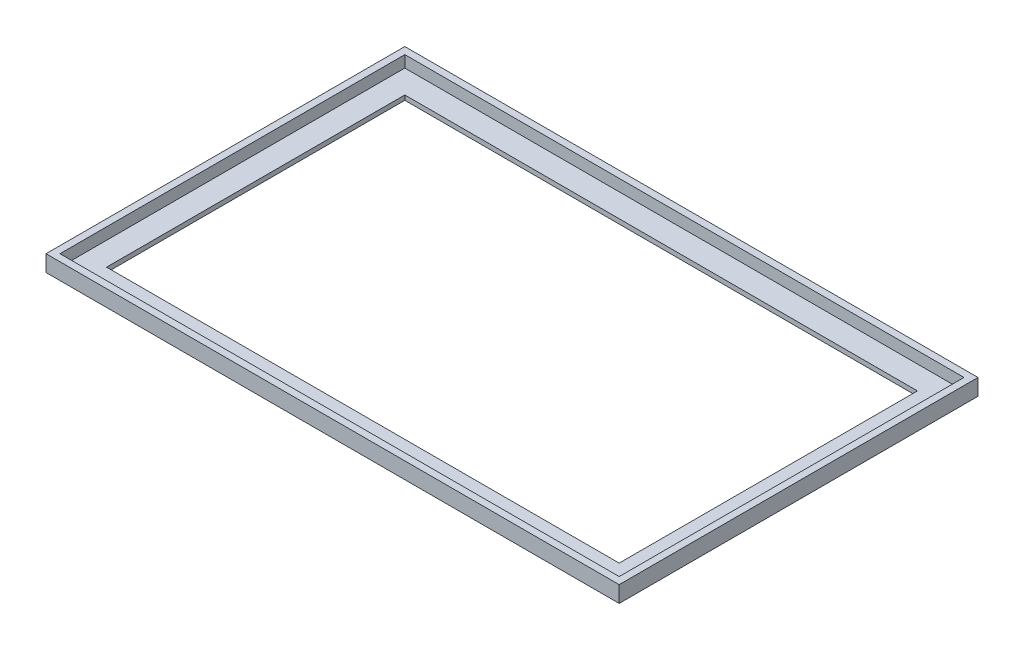
SolidWorks part; units mm, degrees
material "Alumina"
ref_plane "Front Plane" through (0, 0, 0) normal (0, 0, 1) x (1, 0, 0)
ref_plane "Top Plane" through (0, 0, 0) normal (0, 1, 0) x (1, 0, 0)
ref_plane "Right Plane" through (0, 0, 0) normal (1, 0, 0) x (0, 0, -1)
sketch "Sketch1" plane through (0, 0, 0) normal (0, 1, 0) x (1, 0, 0)
  line L1 (-123, -77) -> (123, -77)
  line L2 (-123, -77) -> (-123, 77)
  line L3 (-123, 77) -> (123, 77)
  line L4 (123, -77) -> (123, 77)
  line L5 (-123, -77) -> (123, 77) construction
  line L6 (-123, 77) -> (123, -77) construction
  point P0 (0, 0)
  dimension "D1" = 246
  dimension "D2" = 154
extrude "Boss-Extrude1" add sketch "Sketch1" against normal blind 7
sketch "Sketch2" plane through (0, 0, 0) normal (0, 1, 0) x (1, 0, 0)
  line L1 (-120, -74) -> (120, -74)
  line L2 (-120, -74) -> (-120, 74)
  line L3 (-120, 74) -> (120, 74)
  line L4 (120, -74) -> (120, 74)
  line L5 (-120, -74) -> (120, 74) construction
  line L6 (-120, 74) -> (120, -74) construction
  point P0 (0, 0)
  dimension "D1" = 240
  dimension "D2" = 148
extrude "Cut-Extrude1" cut sketch "Sketch2" against normal blind 5
sketch "Sketch3" plane through (0, -5, 0) normal (0, 1, 0) x (1, 0, 0)
  line L0 (120, 74) -> (-120, 74) construction
  line L1 (-110, -64) -> (110, -64)
  line L2 (-110, -64) -> (-110, 64)
  line L3 (-110, 64) -> (110, 64)
  line L4 (110, -64) -> (110, 64)
  line L5 (-110, -64) -> (110, 64) construction
  line L6 (-110, 64) -> (110, -64) construction
  line L7 (-120, 74) -> (-120, -74) construction
  point P0 (0, 0)
  dimension "D1" = 10
  dimension "D2" = 10
extrude "Cut-Extrude2" cut sketch "Sketch3" against normal blind 5
sketch "Sketch8" plane through (0, -5, 0) normal (0, 1, 0) x (1, 0, 0)
  line L0 (-120, -74) -> (120, -74) construction
  line L1 (-19, -73.1) -> (20, -73.1)
  line L2 (-19, -73.1) -> (-19, -72.8)
  line L3 (-19, -72.8) -> (20, -72.8)
  line L4 (20, -73.1) -> (20, -72.8)
  line L5 (-19, -73.1) -> (20, -72.8) construction
  line L6 (-19, -72.8) -> (20, -73.1) construction
  line L8 (-42.26, -73.1) -> (-30, -73.1)
  line L9 (-42.26, -73.1) -> (-42.26, -72.8)
  line L10 (-42.26, -72.8) -> (-30, -72.8)
  line L11 (-30, -73.1) -> (-30, -72.8)
  line L12 (-42.26, -73.1) -> (-30, -72.8) construction
  line L13 (-42.26, -72.8) -> (-30, -73.1) construction
  point P0 (0.5, -72.95)
  point P7 (-36.13, -72.95)
  dimension "D1" = 19
  dimension "D2" = 20
  dimension "D3" = 0.3
  dimension "D4" = 0.9
  dimension "D5" = 12.26
  dimension "D6" = 30
extrude "Cut-Extrude5" cut sketch "Sketch8" against normal blind 5
sketch "Sketch9" plane through (0, -5, 0) normal (0, 1, 0) x (1, 0, 0)
  line L4 (-120, -74) -> (120, -74) construction
  line L5 (120, -74) -> (120, 74) construction
  circle A0 centre (119, -46.2) radius 0.5
  circle A1 centre (119, -42.7) radius 0.5
  dimension "D1" = 1
  dimension "D2" = 1
  dimension "D3" = 27.8
  dimension "D4" = 31.3
extrude "Cut-Extrude6" cut sketch "Sketch9" against normal blind 5
